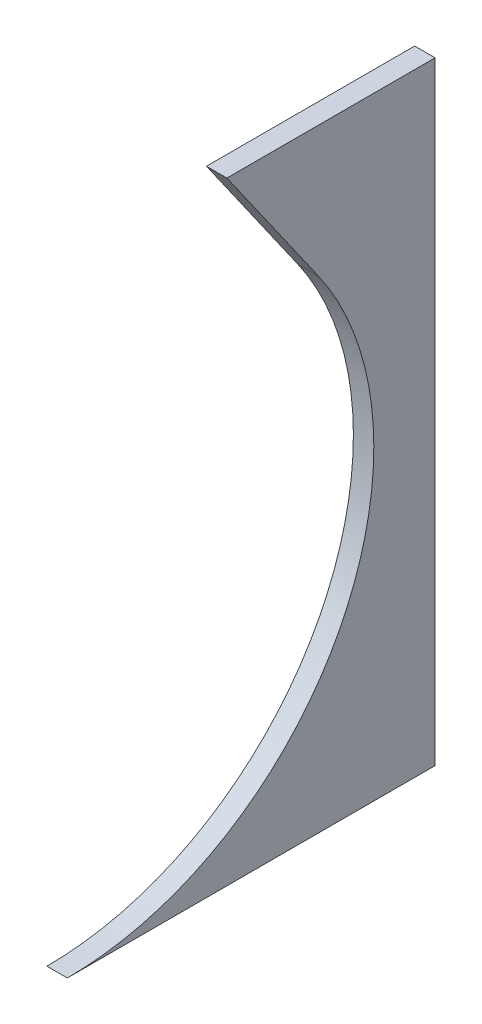
SolidWorks part; units mm, degrees
ref_plane "Front Plane" through (0, 0, 0) normal (0, 0, 1) x (1, 0, 0)
ref_plane "Top Plane" through (0, 0, 0) normal (0, 1, 0) x (1, 0, 0)
ref_plane "Right Plane" through (0, 0, 0) normal (1, 0, 0) x (0, 0, -1)
sketch "Sketch1" plane through (0, 0, 0) normal (1, 0, 0) x (0, 0, -1)
  line L0 (-95.25, 31.75) -> (133.35, 31.75) construction
  line L1 (-95.25, -158.75) -> (133.35, -158.75)
  line L2 (-95.25, -158.75) -> (-95.25, 222.25)
  line L3 (-95.25, 222.25) -> (133.35, 222.25)
  line L4 (133.35, -158.75) -> (133.35, 222.25)
  line L5 (-95.25, -158.75) -> (133.35, 222.25) construction
  line L6 (-95.25, 222.25) -> (133.35, -158.75) construction
  point P0 (0, 0)
  dimension "D1" = 228.6
  dimension "D2" = 381
extrude "Boss-Extrude1" add sketch "Sketch1" along normal blind 12.7
sketch "Sketch2" plane through (12.7, 0, 0) normal (1, 0, 0) x (0, 0, -1)
  line L0 (-95.25, 222.25) -> (-95.25, -158.75) construction
  line L1 (133.35, 222.25) -> (-95.25, 222.25) construction
  circle A0 centre (-95.25, 31.75) radius 190.5
  dimension "D1" = 381
  dimension "D2" = 0
  dimension "D3" = 190.5
extrude "Cut-Extrude1" cut sketch "Sketch2" against normal through all
sketch "Sketch3" plane through (12.7, 0, 0) normal (1, 0, 0) x (0, 0, -1)
  line L1 (60.7985, 141.0163) -> (-14.5807, 248.6689)
  line L2 (60.7985, 141.0163) -> (-203.4462, 141.0163)
  line L5 (-14.5807, 248.6689) -> (-203.4462, 248.6689)
  line L6 (-203.4462, 248.6689) -> (-203.4462, 141.0163)
  arc A0 (-95.25, -158.75) -> (-95.25, 222.25) centre (-95.25, 31.75) ccw construction
  dimension "D1" = 55
extrude "Cut-Extrude2" cut sketch "Sketch3" against normal through all
